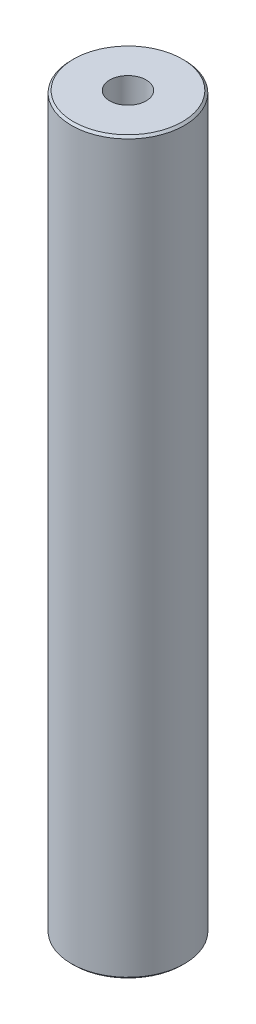
SolidWorks part; units mm, degrees
ref_plane "Front Plane" through (0, 0, 0) normal (0, 0, 1) x (1, 0, 0)
ref_plane "Top Plane" through (0, 0, 0) normal (0, 1, 0) x (1, 0, 0)
ref_plane "Right Plane" through (0, 0, 0) normal (1, 0, 0) x (0, 0, -1)
sketch "Sketch1" plane through (0, 0, 0) normal (0, 1, 0) x (1, 0, 0)
  circle A0 centre (0, 0) radius 37.5
  dimension "SHAFT_OD" = 75
extrude "Boss-Extrude1" add sketch "Sketch1" along normal blind 484.6423
sketch "Sketch2" plane through (0, 0, 0) normal (0, 1, 0) x (1, 0, 0)
  circle A0 centre (0, 0) radius 12.0827
  dimension "BORE_D" = 24.1653
extrude "Cut-Extrude1" cut sketch "Sketch2" along normal through all
chamfer "Chamfer1" distance 1.4096 angle 45 2 edges at (0, 484.6423, 37.5) (0, 0, 37.5)
